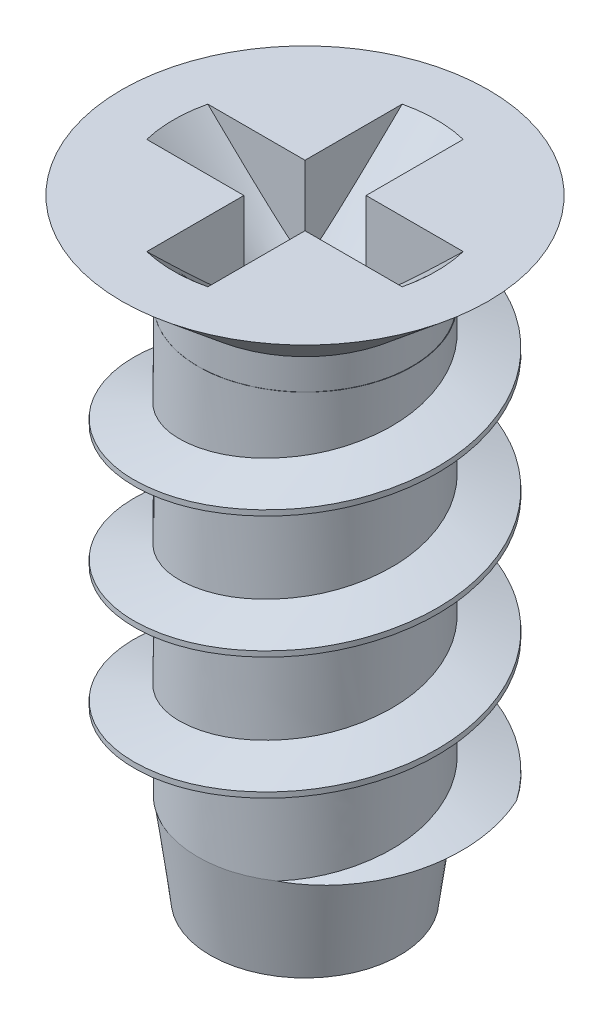
SolidWorks part; units mm, degrees
ref_plane "Спереди" through (0, 0, 0) normal (0, 0, 1) x (1, 0, 0)
ref_plane "Сверху" through (0, 0, 0) normal (0, 1, 0) x (1, 0, 0)
ref_plane "Справа" through (0, 0, 0) normal (1, 0, 0) x (0, 0, -1)
sketch "Эскиз1" plane through (0, 0, 0) normal (0, 0, 1) x (1, 0, 0)
  line L0 (0, 0) -> (0, -10) construction
  line L1 (0, 0) -> (3, 0)
  line L2 (3, 0) -> (1.75, -1.0489)
  line L3 (1.75, -1.0489) -> (1.75, -1.5489)
  line L4 (1.75, -1.5489) -> (2.5, -1.8219)
  line L5 (2.5, -1.8219) -> (2.5, -8.227)
  line L6 (2.5, -8.227) -> (1.75, -8.5)
  line L7 (1.75, -8.5) -> (1.75, -10)
  line L8 (1.75, -10) -> (0, -10)
  line L9 (0, -10) -> (0, 0)
  dimension "D1" = 10
  dimension "D2" = 40
  dimension "D3" = 1.75
  dimension "D4" = 70
  dimension "D5" = 70
  dimension "D6" = 2.5
  dimension "D7" = 1.5
  dimension "D8" = 0.5
  dimension "D9" = 3
revolve "Повернуть1" add sketch "Эскиз1" angle 360 about L0
sketch "Эскиз2" plane through (0, 0, 0) normal (0, 1, 0) x (1, 0, 0)
  line L1 (-0.5, 2.25) -> (0.5, 2.25)
  line L2 (-0.5, 2.25) -> (-0.5, -2.25)
  line L3 (-0.5, -2.25) -> (0.5, -2.25)
  line L4 (0.5, 2.25) -> (0.5, -2.25)
  line L5 (-0.5, 2.25) -> (0.5, -2.25) construction
  line L6 (-0.5, -2.25) -> (0.5, 2.25) construction
  line L7 (-2.25, 0.5) -> (2.25, 0.5)
  line L8 (-2.25, 0.5) -> (-2.25, -0.5)
  line L9 (-2.25, -0.5) -> (2.25, -0.5)
  line L10 (2.25, 0.5) -> (2.25, -0.5)
  line L11 (-2.25, 0.5) -> (2.25, -0.5) construction
  line L12 (-2.25, -0.5) -> (2.25, 0.5) construction
  point P0 (0, 0)
  point P5 (0, 0)
  dimension "D1" = 1
  dimension "D2" = 4.5
extrude "Вырез-Вытянуть1" cut sketch "Эскиз2" against normal blind 1.5 contours L2 L7 L4 L1 | L10 L7 L4 L9 | L2 L9 L4 L7 | L8 L9 L2 L7 | L9 L2 L3 L4 region at (0, 0, -1.375) region at (0, 0, 0) region at (-1.375, 0, 0) region at (1.375, 0, 0) region at (0, 0, 1.375)
sketch "Эскиз3" plane through (0, -10, 0) normal (0, -1, 0) x (1, 0, 0)
  circle A0 centre (0, 0) radius 2.5
curve "Спираль1" pitch 2 height 10 radius 2.5 centre (0, -10, 0) axis (0, 1, 0) start towards (0, 0, -1)
ref_plane "Плоскость1" through (0, -10, -2.5) normal (-0.992, 0.1263, 0) x (0, 0, 1)
sketch "Эскиз4" plane through (0, -10, -2.5) normal (-0.992, 0.1263, 0) x (0, 0, 1)
  line L0 (0, -1.9) -> (0.75, -1.6635)
  line L1 (0.75, -1.6635) -> (0.75, -0.2365)
  line L2 (0.75, -0.2365) -> (0, 0)
  line L3 (0, 0) -> (0, -1.9)
  dimension "D1" = 1.9
  dimension "D2" = 0.75
  dimension "D3" = 35
sweep "Вырез-По траектории1" cut profiles "Эскиз4" path "Спираль1" align with end faces yes
sketch "Эскиз5" plane through (0, 0, 0) normal (0, 0, 1) x (1, 0, 0)
  line L0 (0, -1.5494) -> (-1.75, -1.5489)
  line L1 (-1.75, -1.5489) -> (-1.75, -1.0489)
  line L2 (-1.75, -1.0489) -> (-3, 0)
  line L3 (3, 0) -> (-3, 0) construction
  line L4 (-3, 0) -> (0, 0)
  line L5 (0, 0) -> (0, -1.5494)
  line L6 (0, -1.5) -> (-0.65, -1.5)
  line L7 (0.5, -1.5) -> (-0.5, -1.5) construction
  line L8 (-0.65, -1.5) -> (-2.15, 0)
  spline S0 degree 3 poles (-1.4436, -1.549) (-1.3491, -1.549) (-1.2374, -1.549) (-0.9805, -1.5491) (-0.837, -1.5491) (-0.5329, -1.5492) (-0.3695, -1.5492) (-0.0419, -1.5493) (0.1273, -1.5494) (0.4531, -1.5495) (0.6134, -1.5496) (0.9121, -1.5497) (1.05, -1.5498) (1.2981, -1.5499) (1.4039, -1.55) (1.5793, -1.5502) (1.6462, -1.5503) (1.7349, -1.5505) (1.7567, -1.5506) (1.7528, -1.5508) (1.7269, -1.5509) (1.6308, -1.5511) (1.5595, -1.5512) (1.3785, -1.5514) (1.2687, -1.5516) (1.016, -1.5518) (0.8769, -1.552) (0.5735, -1.5522) (0.4138, -1.5524) (0.086, -1.5527) (-0.0824, -1.5528) (-0.4094, -1.5531) (-0.5718, -1.5533) (-0.7245, -1.5534) knots 0 0 0 0 0.0625 0.0625 0.125 0.125 0.1875 0.1875 0.25 0.25 0.3125 0.3125 0.375 0.375 0.4375 0.4375 0.5 0.5 0.5625 0.5625 0.625 0.625 0.6875 0.6875 0.75 0.75 0.8125 0.8125 0.875 0.875 0.9375 0.9375 1 1 1 1 construction
  dimension "D1" = 40
  dimension "D2" = 45
  dimension "D3" = 0.65
revolve "Повернуть2" add sketch "Эскиз5" angle 360 about L5 region at (-1.7226, -0.8174, 0)
sketch "Эскиз6" plane through (0, 0, 0) normal (0, 1, 0) x (1, 0, 0)
  line L0 (0.5, -0.5) -> (0.5, -1.6825) construction
  line L1 (-2.7418, 0.5) -> (2.7418, 0.5)
  line L2 (-2.7418, 0.5) -> (-2.7418, -0.5)
  line L3 (-2.7418, -0.5) -> (2.7418, -0.5)
  line L4 (2.7418, 0.5) -> (2.7418, -0.5)
  line L5 (-2.7418, 0.5) -> (2.7418, -0.5) construction
  line L6 (-2.7418, -0.5) -> (2.7418, 0.5) construction
  line L7 (-0.5, 2.4322) -> (0.5, 2.4322)
  line L8 (-0.5, 2.4322) -> (-0.5, -2.4322)
  line L9 (-0.5, -2.4322) -> (0.5, -2.4322)
  line L10 (0.5, 2.4322) -> (0.5, -2.4322)
  line L11 (-0.5, 2.4322) -> (0.5, -2.4322) construction
  line L12 (-0.5, -2.4322) -> (0.5, 2.4322) construction
  line L13 (0.5, 0.5) -> (2.0911, 0.5) construction
  circle A0 centre (0, 0) radius 2.15
  arc M1 (1.3842, -1.6452) -> (-0.7371, 2.0197) centre (0, 0) cw
  line M4 (-1.6778, 0.5) -> (-0.5, 0.5)
  line M5 (-0.5, 0.5) -> (-0.5, 2.0911)
  line M7 (0.5, 2.0911) -> (0.5, 0.5)
  line M8 (0.5, 0.5) -> (2.0911, 0.5)
  line M10 (2.0911, -0.5) -> (0.5, -0.5)
  line M11 (0.5, -0.5) -> (0.5, -1.6825)
  line M13 (1.1522, -1.326) -> (1.3842, -1.6452)
extrude "Бобышка-Вытянуть1" add sketch "Эскиз6" against normal blind 0.5 contours A0 M5 M4 | L1 M1 | A0 M8 M7 | A0 M13 M10 M11 | L10 M1 M13 | L8 L3 M1 region at (-1.1288, 0, -1.1288) region at (1.1288, 0, -1.1288) region at (-1.1288, 0, 1.1288) region at (1.1288, 0, 1.1288)
sketch "Эскиз7" plane through (0, 0, 0) normal (0, 0, 1) x (1, 0, 0)
  line L0 (0, 0) -> (0, -9.9771) construction
  line L1 (1.75, -8.5) -> (1.55, -10)
  line L2 (-1.75, -10) -> (1.75, -10) construction
  line L3 (1.55, -10) -> (1.75, -10)
  line L4 (1.75, -10) -> (1.75, -8.5)
  dimension "D1" = 1.55
revolve "Вырез-Повернуть1" cut sketch "Эскиз7" angle 360 about L0
